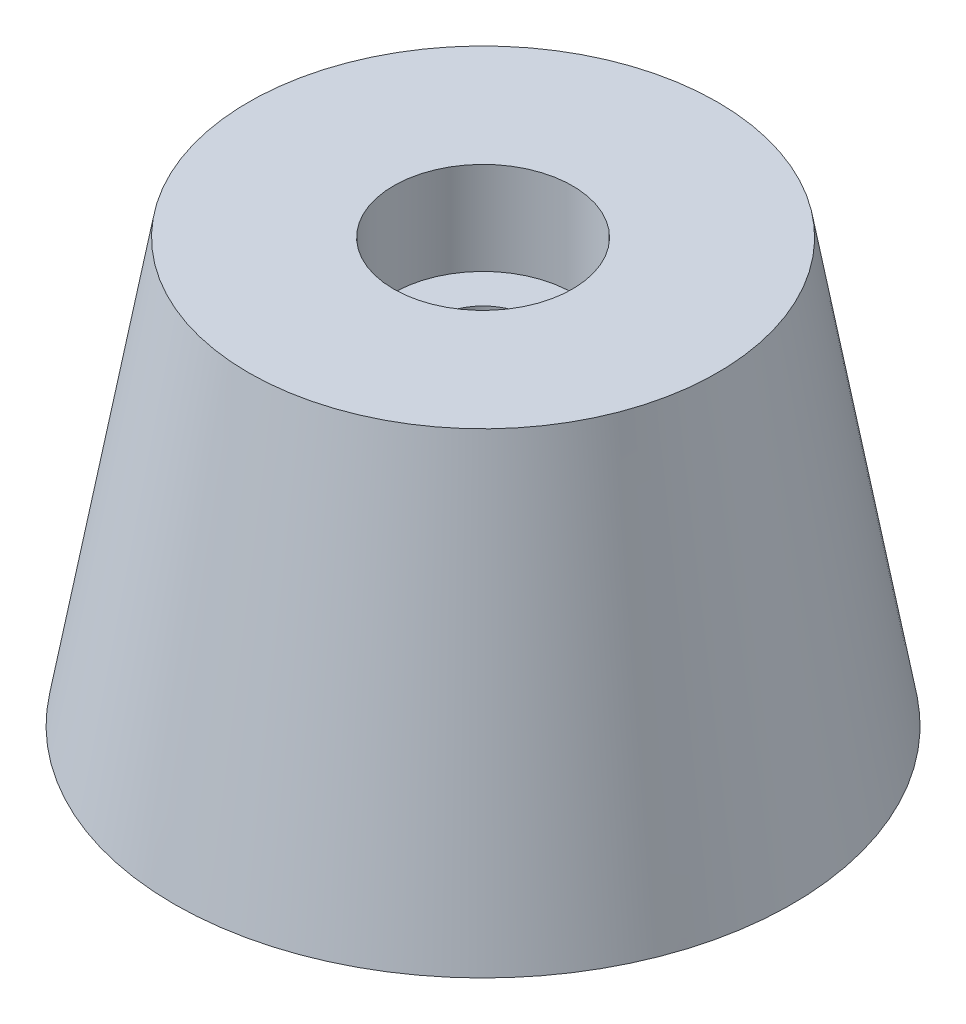
SolidWorks part; units mm, degrees
ref_plane "Front Plane" through (0, 0, 0) normal (0, 0, 1) x (1, 0, 0)
ref_plane "Top Plane" through (0, 0, 0) normal (0, 1, 0) x (1, 0, 0)
ref_plane "Right Plane" through (0, 0, 0) normal (1, 0, 0) x (0, 0, -1)
sketch "Sketch1" plane through (0, 0, 0) normal (0, 1, 0) x (1, 0, 0)
  circle A0 centre (0, 0) radius 19
  dimension "D1" = 38
extrude "Boss-Extrude1" add sketch "Sketch1" along normal blind 26 draft 10
hole_wizard "CBORE for M5 Pan Head Machine Screw1" positions "Sketch3" profile "Sketch2" counterbore size "M5" standard "ANSI Metric" end condition through all
sketch "Sketch3" plane through (0, 26, 0) normal (0, 1, 0) x (1, 0, 0)
  point P0 (0, 0)
sketch "Sketch2" plane through (0, 26, 0) normal (1, 0, 0) x (0, 0, 1)
  line L0 (0, 0) -> (0, 26)
  line L1 (0, 26) -> (2.9, 26)
  line L3 (2.9, 26) -> (2.9, 5.7)
  line L4 (2.9, 5.7) -> (5.5, 5.7)
  line L5 (5.5, 5.7) -> (5.5, 0)
  line L7 (5.5, 0) -> (0, 0)
  line L11 (0, -6.35) -> (0, 107.95) construction
  dimension "Thru Hole Dia." = 5.8
  dimension "Thru Hole Depth" = 26
  dimension "C'Bore Dia." = 11
  dimension "C'Bore Depth" = 5.7
